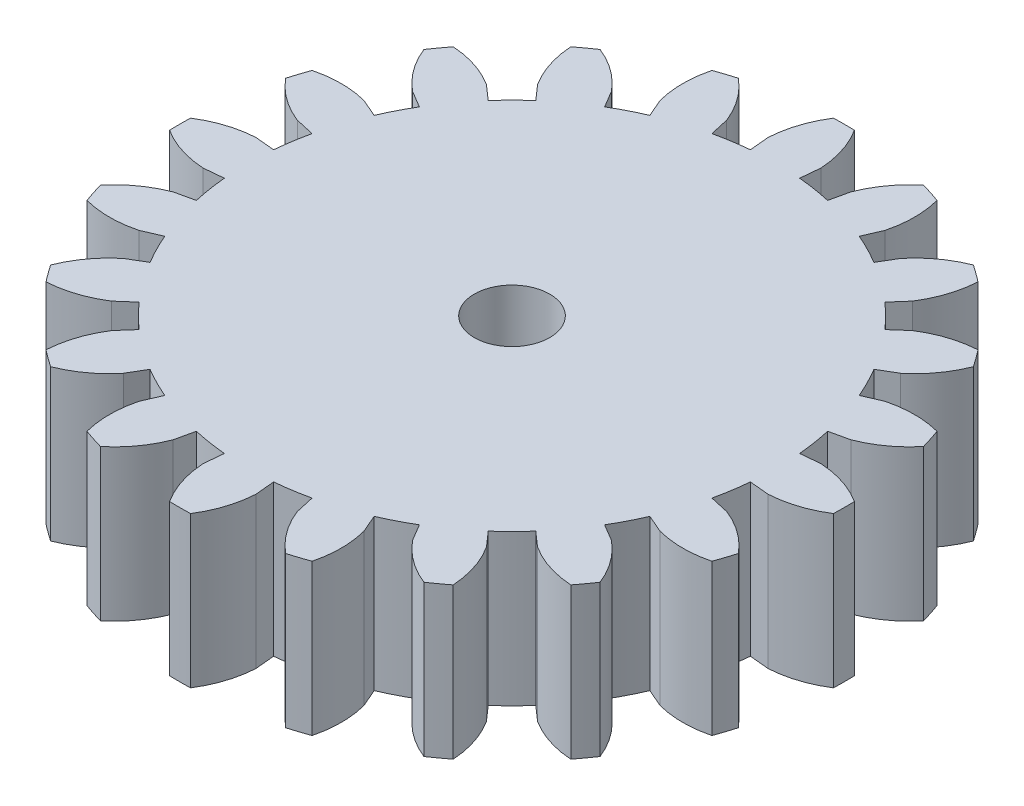
SolidWorks part; units mm, degrees
ref_plane "Спереди" through (0, 0, 0) normal (0, 0, 1) x (1, 0, 0)
ref_plane "Сверху" through (0, 0, 0) normal (0, 1, 0) x (1, 0, 0)
ref_plane "Справа" through (0, 0, 0) normal (1, 0, 0) x (0, 0, -1)
other "Configuration Table"
sketch "Эскиз1" plane through (0, 0, 0) normal (0, 1, 0) x (1, 0, 0)
  circle A0 centre (0, 0) radius 17.5
  dimension "D1" = 35
extrude "Бобышка-Вытянуть1" add sketch "Эскиз1" along normal blind 10
sketch "Эскиз2" plane through (0, 0, 0) normal (0, -1, 0) x (1, 0, 0)
  line L0 (0, 0) -> (0, 22) construction
  line L1 (0, 0) -> (-1.7523, 18.712) construction
  line L2 (0, 0) -> (1.7523, 18.712) construction
  line L5 (-1.5692, 19.9383) -> (0, 0) construction
  line L6 (0, 0) -> (1.5692, 19.9383) construction
  line L7 (-0.6949, 21.989) -> (0, 0) construction
  line L8 (-1.6317, 17.4238) -> (-1.7523, 18.712)
  line L9 (1.7523, 18.712) -> (1.6317, 17.4238)
  circle A0 centre (0, 0) radius 18.7938 construction
  circle A1 centre (0, 0) radius 20 construction
  circle A2 centre (0, 0) radius 22 construction
  arc A3 (-0.6949, 21.989) -> (0.6949, 21.989) centre (0, 0) cw
  arc A4 (-1.6317, 17.4238) -> (1.6317, 17.4238) centre (0, 0) cw
  circle A5 centre (0, 0) radius 17.5 construction
  arc A6 (-1.5692, 19.9383) -> (1.5692, 19.9383) centre (0, 0) cw construction
  arc A7 (-1.7523, 18.712) -> (-0.6949, 21.989) centre (5.0681, 18.3203) cw
  arc A8 (0.6949, 21.989) -> (1.7523, 18.712) centre (-5.0681, 18.3203) cw
  point P12 (0, 20)
  point P16 (0, 22)
  point P22 (0, 17.5)
  dimension "D1" = 37.5877
  dimension "D2" = 40
  dimension "D3" = 44
  dimension "D4" = 5.35
  dimension "D5" = 4.5
  dimension "D6" = 1.81
extrude "Бобышка-Вытянуть2" add sketch "Эскиз2" against normal blind 10
pattern_circular "Круговой массив1" count 20 over 360 about axis through (0, 10, 0) along (0, -1, 0) of "Бобышка-Вытянуть2" reverse direction yes
sketch "Эскиз3" plane through (0, 0, 0) normal (0, -1, 0) x (1, 0, 0)
  circle A0 centre (0, 0) radius 2.5
  dimension "D1" = 5
extrude "Вырез-Вытянуть1" cut sketch "Эскиз3" against normal through all
equation "\"Ширина груза\"= 420"
equation "\"Глубина груза\"= 490"
equation "\"Высота груза\"= 297"
equation "\"Ширина ячейки\"= \"Ширина груза\" + 10"
equation "\"Глубина ячейки\"= \"Глубина груза\" + 10"
equation "\"Высота ячейки\"= \"Высота груза\" + 10 + 13"
equation "\"Колво ячеек ширина\"= 2"
equation "\"Колво ячеек высота\"= 2"
equation "\"Толщина стенки\"= 10"
equation "\"Крепление дверцы\"= 5"
equation "\"Ширина рейки\"= \"Толщина шестерни\""
equation "\"Высота рейки\"= 20"
equation "\"Высота пола\"= 20"
equation "\"Колво полозьев\"= 5"
equation "\"Отступ рейки\"= 20"
equation "\"Глубина каретки\"= \"Глубина ячейки\" + 30 + \"Мотор Y высота корпуса\" + 20"
equation "\"Длинна рейки\"= ( \"Ширина ячейки\" + \"Толщина стенки\" + \"Крепление дверцы\" ) * \"Колво ячеек ширина\" + \"Ширина ячейки выгрузки\" * \"Колво выгрузки\" + \"Толщина стенки\""
equation "\"Отступ шпильки\"= 20"
equation "\"Диаметр шпильки\"= 5"
equation "\"Длинна шпильки\"= ( \"Высота ячейки\" + \"Толщина стенки\" + \"Высота пола\" ) * \"Колво ячеек высота\" + ( \"Толщина стенки\" + \"Отступ рейки\" ) * 2 "
equation "\"Ширина пластины\"= 50  "
equation "\"Высота зона выгрузки\"= \"Высота ячейки\" * 2 + \"Толщина стенки\" * 2"
equation "\"Колво выгрузки\"= 1"
equation "\"Ширина ячейки выгрузки\"= \"Ширина ячейки\" + \"Толщина стенки\" + \"Отступ крепления мотора фиксации\"*2"
equation "\"Отступ крепления мотора фиксации\" = 30"
equation "\"Мотор X ширина корпуса\"= 42.3"
equation "\"Мотор X высота корпуса\"= 42.3"
equation "\"Мотор X длина корпуса\"= 40"
equation "\"Мотор X вылет вала\"= 19.8"
equation "\"Мотор Y ширина корпуса\"= 42.3"
equation "\"Мотор Y высота корпуса\"= 42.3"
equation "\"Мотор Y длина корпуса\"= 48"
equation "\"Мотор Y вылет вала\"= 30"
equation "\"Мотор Z ширина корпуса\"= 42"
equation "\"Мотор Z высота корпуса\"= 42"
equation "\"Мотор Z длина корпуса\"= 40"
equation "\"Мотор Z вылет вала\"= 23"
equation "\"Мотор диаметр вала ПРЕДВ\"= 5"
equation "\"Мотор шаг крепления ПРЕДВ\"= 31"
equation "\"Мотор диаметр отверстий ПРЕДВ\"= 3"
equation "\"Мотор глубина отверстий ПРЕДВ\"= 4.5"
equation "\"Мотор диаметр буртика ПРЕДВ\"= 22"
equation "\"Мотор высота буртика ПРЕДВ\"= 2"
equation "\"Мотор диаметр шкива ПРЕДВ\"= 16"
equation "\"Мотор длина шкива ПРЕДВ\"= 12"
equation "\"Мотор отступ шкива ПРЕДВ\"= 5"
equation "\"Мотор X шаг градусов\"= 1.8"
equation "\"Мотор Y шаг градусов\"= 1.8"
equation "\"Мотор Z шаг градусов\"= 1.8"
equation "\"Мотор Y диаметр ротора\"= 25.78"
equation "\"Толщина шестерни\"= 10"
equation "\"D1@Бобышка-Вытянуть1\"=\"Толщина шестерни\""
equation "\"D1@Бобышка-Вытянуть2\"=\"Толщина шестерни\""
equation "\"D1@Эскиз3\"=\"Мотор диаметр вала ПРЕДВ\""
